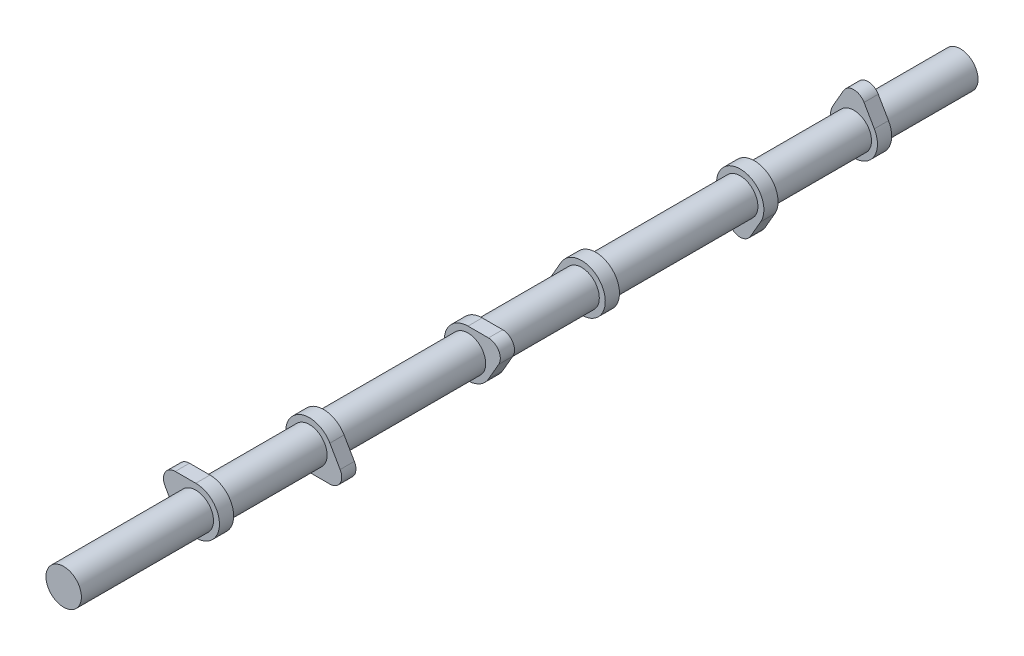
SolidWorks part; units mm, degrees
material "Plain Carbon Steel"
ref_plane "Front Plane" through (0, 0, 0) normal (0, 0, 1) x (1, 0, 0)
ref_plane "Top Plane" through (0, 0, 0) normal (0, 1, 0) x (1, 0, 0)
ref_plane "Right Plane" through (0, 0, 0) normal (1, 0, 0) x (0, 0, -1)
sketch "Sketch1" plane through (0, 0, 0) normal (0, 0, 1) x (1, 0, 0)
  line L0 (-5.4993, 15.875) -> (-10.9985, 6.35)
  line L1 (5.4993, 15.875) -> (10.9985, 6.35)
  arc A0 (-10.9985, 6.35) -> (10.9985, 6.35) centre (0, 0) ccw
  arc A2 (5.4993, 15.875) -> (-5.4993, 15.875) centre (0, 12.7) ccw
  dimension "D1" = 25.4
  dimension "D2" = 6.35
  dimension "D3" = 12.7
extrude "Boss-Extrude1" add sketch "Sketch1" along normal mid plane 7.62
ref_axis "Axis1" through (0, 0, 149.0714) along (0, 0, -1)
move or copy body "Body-Move/Copy1" bodies to move or copy 101 copy yes number of copies 1 translate (0, 0, 60.96)
move or copy body "Body-Move/Copy2" bodies to move or copy 102 copy no rotation origin (0, 0, 0) rotation axis (0, 0, 1) rotation angle 180
sketch "Sketch2" plane through (0, 0, 0) normal (0, 0, 1) x (1, 0, 0)
  circle A0 centre (0, 0) radius 9.5
  dimension "D1" = 19
extrude "Boss-Extrude2" add sketch "Sketch2" along normal blind 146.05 from offset 25.4 offset against normal yes
pattern_linear "LPattern1" count 3 spacing 146.05 along (0, 0, 1) of bodies 104
move or copy body "Body-Move/Copy3" bodies to move or copy 105 copy no rotation origin (0, 0, 0) rotation axis (0, 0, 1) rotation angle 120
move or copy body "Body-Move/Copy4" bodies to move or copy 106 copy no rotation origin (0, 0, 0) rotation axis (0, 0, -1) rotation angle 120
sketch "Sketch3" plane through (0, 0, -25.4) normal (0, 0, -1) x (-1, 0, 0)
  circle A1 centre (0, 0) radius 9.5
  circle A2 centre (0, 0) radius 9.5
  dimension "D1" = 0
extrude "Boss-Extrude3" add sketch "Sketch3" along normal blind 27.94
combine bodies "Combine1" operation type add bodies to combine 109 107 108
sketch "Sketch4" plane through (0, 0, 412.75) normal (0, 0, 1) x (1, 0, 0)
  circle A1 centre (0, 0) radius 9.5
  circle A2 centre (0, 0) radius 9.5
  dimension "D1" = 0
extrude "Boss-Extrude4" add sketch "Sketch4" along normal blind 15
